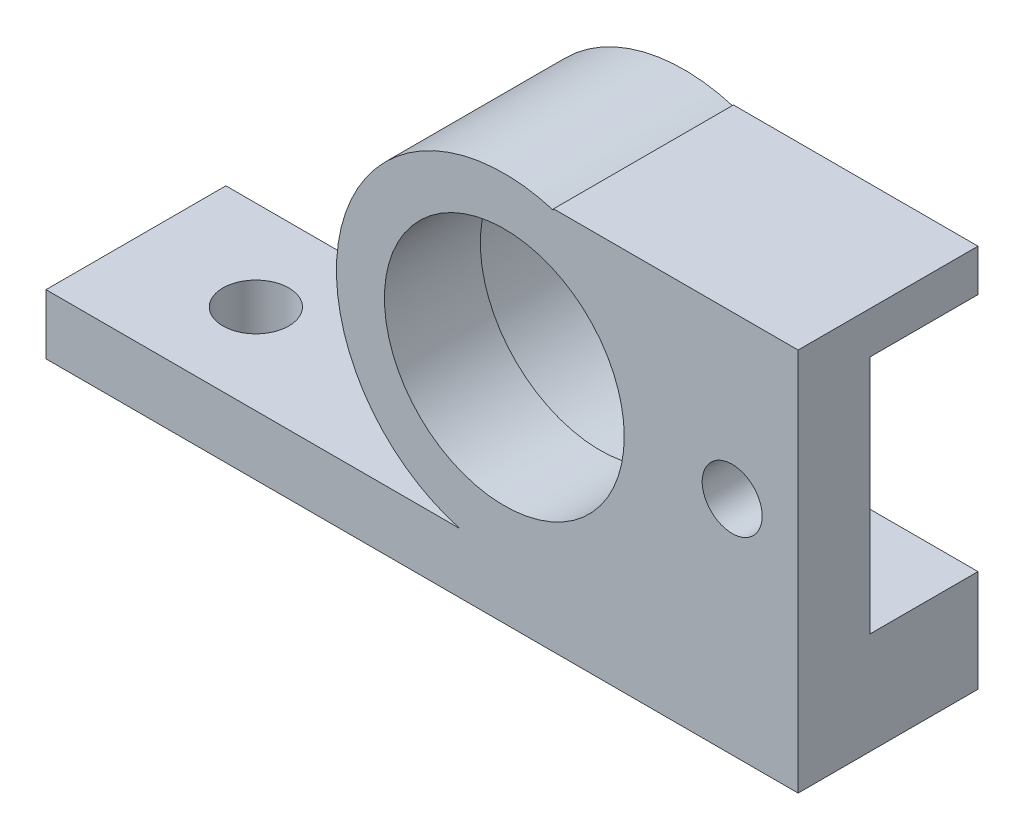
SolidWorks part; units mm, degrees
ref_plane "前视基准面" through (0, 0, 0) normal (0, 0, 1) x (1, 0, 0)
ref_plane "上视基准面" through (0, 0, 0) normal (0, 1, 0) x (1, 0, 0)
ref_plane "右视基准面" through (0, 0, 0) normal (1, 0, 0) x (0, 0, -1)
sketch "草图1" plane through (0, 0, 0) normal (0, 0, 1) x (1, 0, 0)
  line L1 (20, -10) -> (-20, -10)
  line L2 (20, -10) -> (20, 10)
  line L3 (20, 10) -> (-20, 10)
  line L4 (-20, -10) -> (-20, 10)
  line L5 (20, -10) -> (-20, 10) construction
  line L6 (20, 10) -> (-20, -10) construction
  point P0 (0, 0)
  dimension "D1" = 40
  dimension "D2" = 20
extrude "凸台-拉伸1" add sketch "草图1" along normal blind 6
sketch "草图2" plane through (0, 0, 6) normal (0, 0, 1) x (1, 0, 0)
  line L0 (20, -10) -> (20, 10) construction
  circle A0 centre (10, 0) radius 2.5
  circle A1 centre (-1, 0) radius 2.5
  circle A2 centre (-12, 0) radius 2.5
  dimension "D1" = 10
  dimension "D2" = 5
  dimension "D3" = 3
extrude "切除-拉伸1" cut sketch "草图2" against normal through all
sketch "草图3" plane through (0, 0, 6) normal (0, 0, 1) x (1, 0, 0)
  line L0 (20, 13.5) -> (20, 10)
  line L1 (20, -13.5) -> (-26.894, -13.5)
  line L3 (20, 13.5) -> (-26.894, 13.5)
  line L4 (-20, 10) -> (-20, -10)
  line L5 (-20, -10) -> (20, -10)
  line L6 (20, -10) -> (20, 10)
  line L7 (20, 10) -> (-20, 10)
  line L8 (-20, 10) -> (-20, -10)
  line L9 (-20, -10) -> (20, -10)
  line L10 (20, -10) -> (20, 10)
  line L11 (20, 10) -> (-20, 10)
  line L12 (-26.894, -13.5) -> (-26.894, 13.5)
  line L13 (20, -10.0394) -> (-26.894, 13.5) construction
  line L14 (20, 10.0394) -> (-26.894, -13.5) construction
  line L15 (20, -10) -> (20, -13.5)
  circle A0 centre (-31, 0) radius 11
  circle A1 centre (-31, 0) radius 14
  point P2 (0, 0)
  line M10 (-20, 10) -> (-20, -10)
  line M11 (-20, -10) -> (20, -10)
  line M13 (20, 10) -> (-20, 10)
  dimension "D3" = 22
  dimension "D4" = 28
  dimension "D2" = 3.5
  dimension "D1" = 0
extrude "凸台-拉伸2" add sketch "草图3" against normal blind 15 contours L3 A1 L1 L12 A0 | A1 L1 L15 M11 M10 | L1 A1 L8 A0 L12 | L8 A1 L3 L12 A0 | L8 A1 | A1 L0 L3 M10 M13 region at (-1.9449, 11.7771, 6) region at (-1.9449, -11.7771, 6) region at (-23.0173, 9.0328, 6) region at (-27.2274, 11.7946, 6) region at (-18.7882, 0, 6) region at (-23.0173, -9.0328, 6)
sketch "草图5" plane through (0, 0, 6) normal (0, 0, 1) x (1, 0, 0)
  circle A0 centre (-31, 0) radius 10
  circle A1 centre (-31, 0) radius 11 construction
  circle A2 centre (-31, 0) radius 11
  dimension "D1" = 20
extrude "凸台-拉伸3" add sketch "草图5" against normal blind 8
sketch "草图6" plane through (0, 0, 6) normal (0, 0, 1) x (1, 0, 0)
  circle A0 centre (-31, 0) radius 8.5
  circle A1 centre (-31, 0) radius 10 construction
  circle A2 centre (-31, 0) radius 10
  dimension "D1" = 17
sketch "草图8" plane through (0, 0, 6) normal (0, 0, 1) x (1, 0, 0)
  line L0 (20, -13.5) -> (20, 13.5) construction
  line L1 (20, -13.5) -> (-26.894, -13.5) construction
  line L2 (20, 13.5) -> (-26.894, 13.5) construction
  line L3 (20, -13.5) -> (20, 13.5)
  line L4 (20, -13.5) -> (-26.894, -13.5)
  line L5 (20, 13.5) -> (-26.894, 13.5)
  line L6 (-45, -14) -> (-26.894, -13.5)
  line L7 (-45, -14) -> (-239, -14)
  line L8 (-45, -14) -> (-45, 14)
  line L9 (-45, 14) -> (-239, 14)
  line L10 (-239, -14) -> (-239, 14)
  line L11 (-45, -14) -> (-239, 14) construction
  line L12 (-45, 14) -> (-239, -14) construction
  line L13 (-45, 14) -> (-26.894, 13.3843)
  line L14 (-12, 0) -> (-31, 0)
  arc A0 (-26.894, 13.3843) -> (-26.894, -13.3843) centre (-31, 0) ccw construction
  arc A1 (-26.894, 13.3843) -> (-26.894, -13.3843) centre (-31, 0) ccw
  point P6 (-142, 0)
  dimension "D1" = 28
  dimension "D2" = 194
  dimension "D3" = 14
sketch "草图9" plane through (0, -13.5, 0) normal (0, -1, 0) x (1, 0, 0)
  circle A0 centre (10.5344, 0) radius 5.2388
sketch "草图10" plane through (20, 0, 0) normal (1, 0, 0) x (0, 0, -1)
  line L1 (9, -13.5) -> (-6, -13.5)
  line L2 (9, -13.5) -> (9, -18.5)
  line L3 (9, -18.5) -> (-6, -18.5)
  line L4 (-6, -13.5) -> (-6, -18.5)
  dimension "D1" = 5
extrude "凸台-拉伸4" add sketch "草图10" against normal blind 500
sketch "草图11" plane through (0, 0, -9) normal (0, 0, -1) x (-1, 0, 0)
  line L1 (22.0371, -11.3638) -> (33.5283, -11.3638)
  line L2 (22.0371, -11.3638) -> (22.0371, -16.4864)
  line L3 (22.0371, -16.4864) -> (33.5283, -16.4864)
  line L4 (33.5283, -11.3638) -> (33.5283, -16.4864)
extrude "凸台-拉伸5" add sketch "草图11" against normal through all
sketch "草图12" plane through (0, 0, 6) normal (0, 0, 1) x (1, 0, 0)
  line L0 (-12, 0) -> (-1, 0) construction
  line L1 (-6.5, 0) -> (-6.5, 13.5) construction
  line L2 (20, 13.5) -> (-26.894, 13.5) construction
  line L4 (-6.5, 13.5) -> (20, 13.5)
  line L5 (-6.5, 13.5) -> (-6.5, -18.5)
  line L6 (-6.5, -18.5) -> (20, -18.5)
  line L7 (20, 13.5) -> (20, -18.5)
extrude "切除-拉伸2" cut sketch "草图12" against normal through all
sketch "草图13" plane through (0, -18.5, 0) normal (0, -1, 0) x (1, 0, 0)
  line L0 (-69.2198, 6) -> (-69.2198, -9.0491)
  line L1 (-480, 6) -> (-6.5, 6) construction
  line L2 (-69.2198, 131.4142) -> (-69.2198, -238.5858) construction
sketch "草图14" plane through (0, -18.5, 0) normal (0, -1, 0) x (1, 0, 0)
  line L1 (-69.2198, -9.0491) -> (-494.0275, -9.0491)
  line L2 (-69.2198, -9.0491) -> (-69.2198, 12.8124)
  line L3 (-69.2198, 12.8124) -> (-494.0275, 12.8124)
  line L4 (-494.0275, -9.0491) -> (-494.0275, 12.8124)
extrude "切除-拉伸3" cut sketch "草图14" against normal through all
sketch "草图15" plane through (0, -18.5, 0) normal (0, -1, 0) x (1, 0, 0)
  line L0 (-59.2198, 6) -> (-59.2198, -9)
  line L1 (-45, 6) -> (-239, 6) construction
  line L2 (-69.2198, -9) -> (-6.5, -9) construction
  line L3 (-69.2198, 6) -> (-69.2198, -9.0491) construction
  circle A0 centre (-59.2198, -1.5) radius 2.75
  dimension "D2" = 5.5
  dimension "D1" = 10
extrude "切除-拉伸4" cut sketch "草图15" against normal blind 10 contours A0
